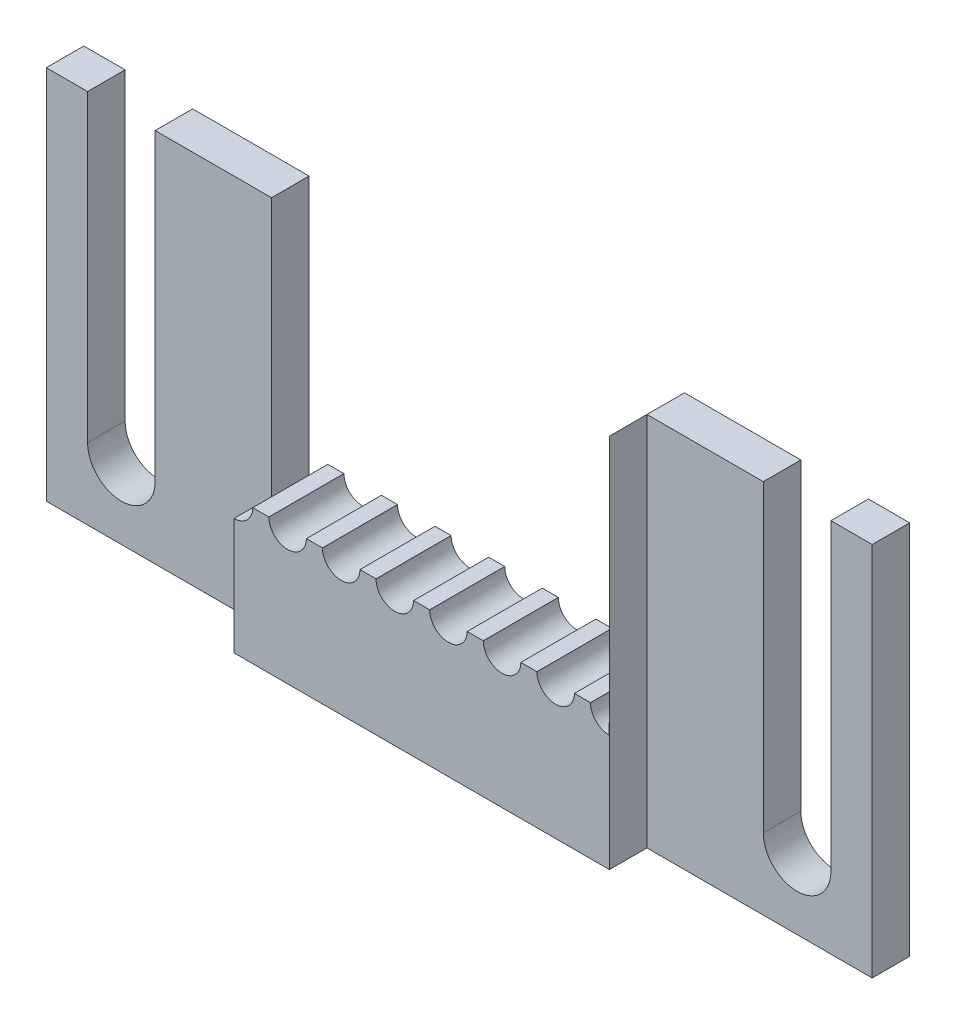
SolidWorks part; units mm, degrees
ref_plane "Přední rovina" through (0, 0, 0) normal (0, 0, 1) x (1, 0, 0)
ref_plane "Horní rovina" through (0, 0, 0) normal (0, 1, 0) x (1, 0, 0)
ref_plane "Pravá rovina" through (0, 0, 0) normal (1, 0, 0) x (0, 0, -1)
sketch "Skica1" plane through (0, 0, 0) normal (0, 0, 1) x (1, 0, 0)
  line L1 (-27.5, 12.5) -> (27.5, 12.5)
  line L2 (-27.5, 12.5) -> (-27.5, -12.5)
  line L3 (-27.5, -12.5) -> (27.5, -12.5)
  line L4 (27.5, 12.5) -> (27.5, -12.5)
  line L5 (-27.5, 12.5) -> (27.5, -12.5) construction
  line L6 (-27.5, -12.5) -> (27.5, 12.5) construction
  point P0 (0, 0)
  dimension "D1" = 55
  dimension "D2" = 25
extrude "Přidat vysunutím1" add sketch "Skica1" along normal blind 5
sketch "Skica2" plane through (0, 0, 5) normal (0, 0, 1) x (1, 0, 0)
  line L0 (27.5, 12.5) -> (-27.5, 12.5) construction
  line L1 (-12.5, 12.5) -> (-12.5, 0)
  line L2 (-12.5, -3.5) -> (18.5208, -3.5)
  line L3 (12.5, 12.5) -> (12.49, -4.75)
  line L4 (12.5, 0) -> (-12.5, 0)
  line L5 (-12.5, 0) -> (-12.5, -3.5)
  line L7 (-12.5, -3.5) -> (-12.5, -4.75)
  line L8 (-12.5, -4.75) -> (12.49, -4.75)
  circle A0 centre (0, 12.5) radius 12.5
  circle A1 centre (-12.5, -3.5) radius 1.25
  circle A2 centre (-8.93, -3.5) radius 1.25
  circle A3 centre (-5.36, -3.5) radius 1.25
  circle A4 centre (-1.79, -3.5) radius 1.25
  circle A5 centre (1.78, -3.5) radius 1.25
  circle A6 centre (5.35, -3.5) radius 1.25
  circle A7 centre (8.92, -3.5) radius 1.25
  circle A8 centre (12.49, -3.5) radius 1.25
  line M2 (27.5, 12.5) -> (-27.5, 12.5)
  dimension "D1" = 25
  dimension "D3" = 2.5
  dimension "D2" = 16
  dimension "D4" = 8
extrude "Odebrat vysunutím1" cut sketch "Skica2" against normal blind 10 contours L7 A1 L2 | L2 A1 L5 | L2 A2 | L2 A2 | L2 A8 | A8 L4 L5 A1 L2 A2 A3 A4 A5 A6 A7 | A0 L1 L4 | L3 A8 L2 | A0 M2 | A0 L4 L3 | A3 | A4 | A5 | A6 | A7 | A2 region at (-9.7079, 2.7921, 5) region at (9.7041, 2.7902, 5) region at (0, 7.1948, 5) region at (-0.0042, -1.4519, 5) region at (-11.9695, -2.9695, 5) region at (-11.9695, -4.0305, 5) region at (11.9601, -2.9693, 5) region at (-8.93, -2.9695, 5) region at (-8.93, -4.0305, 5) region at (11.9597, -4.0305, 5)
sketch "Skica3" plane through (0, 0, 5) normal (0, 0, 1) x (1, 0, 0)
  line L1 (-12.5, 12.5) -> (-27.5, 12.5)
  line L3 (-20, 12.5) -> (-20, -12.5)
  line L4 (-27.5, -12.5) -> (27.5, -12.5) construction
  line L5 (0, 0) -> (0, 10.0912)
  line L6 (-12.5, -12.5) -> (-27.5, -12.5)
  line L7 (-12.5, -12.5) -> (-12.5, 12.5)
  line L8 (-12.5, 12.5) -> (-27.5, 12.5)
  line L9 (-27.5, -12.5) -> (-27.5, 12.5)
  line L10 (-12.5, -12.5) -> (-27.5, 12.5) construction
  line L11 (-12.5, 12.5) -> (-27.5, -12.5) construction
  line L12 (27.5, -12.5) -> (27.5, 12.5)
  line L13 (12.5, -12.5) -> (27.5, -12.5)
  line L14 (12.5, -12.5) -> (12.5, 12.5)
  line L15 (12.5, 12.5) -> (27.5, 12.5)
  point P7 (-20, 0)
  line M1 (-12.5, -4.75) -> (-12.5, 12.5)
  line M2 (-12.5, 12.5) -> (-27.5, 12.5)
  line M3 (-27.5, 12.5) -> (-27.5, -12.5)
  line M4 (-27.5, -12.5) -> (27.5, -12.5)
  line M5 (27.5, -12.5) -> (27.5, 12.5)
  line M6 (27.5, 12.5) -> (12.5, 12.5)
extrude "Odebrat vysunutím2" cut sketch "Skica3" against normal blind 2.5 contours M6 M4 M5 | M1 M2 M3 M4 | L3 L1 M3 M4 region at (-16.25, 0, 5) region at (20, 0, 5) region at (-23.75, 0, 5)
sketch "Skica4" plane through (0, 0, 2.5) normal (0, 0, 1) x (1, 0, 0)
  line L0 (0, 0) -> (22.5, 0)
  line L1 (22.5, 0) -> (22.5, 2.5)
  line L2 (0, 0) -> (0, -18.9556)
  line L3 (-22.5, 0) -> (-22.5, 2.5)
  dimension "D1" = 22.5
  dimension "D2" = 2.5
hole_wizard "M4 díra s vůlí4" positions "Skica11" profile "Skica12" size "M4" standard "ISO" slot yes end condition through all
sketch "Skica11" plane through (0, 0, 2.5) normal (0, 0, 1) x (1, 0, 0)
  line L0 (22.5, -10) -> (22.5, 15) construction
  point P0 (22.5, 2.5)
  point P6 (-22.5, 2.5)
  dimension "D1" = 25
sketch "Skica12" plane through (22.5, 2.5, 2.5) normal (1, 0, 0) x (0, -1, 0)
  line L0 (0, 0) -> (0, 2.5)
  line L1 (0, 2.5) -> (2.25, 2.5)
  line L2 (2.25, 2.5) -> (2.25, 0)
  line L5 (2.25, 0) -> (0, 0)
  line L11 (0, -6.35) -> (0, 107.95) construction
  dimension "Průměr díry skrz" = 4.5
  dimension "Hloubka díry skrz" = 2.5
